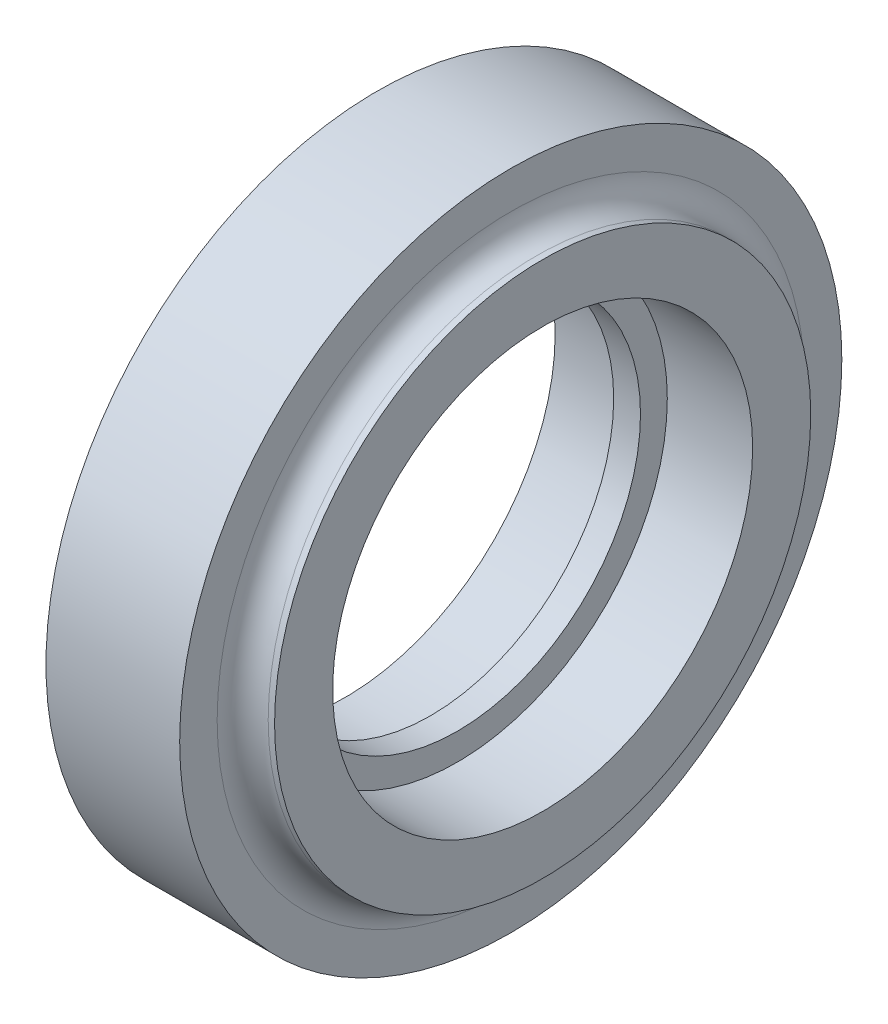
SolidWorks part; units mm, degrees
material "AISI 1020"
ref_plane "Front" through (0, 0, 0) normal (0, 0, 1) x (1, 0, 0)
ref_plane "Top" through (0, 0, 0) normal (0, 1, 0) x (1, 0, 0)
ref_plane "Right" through (0, 0, 0) normal (1, 0, 0) x (0, 0, -1)
sketch "Sketch1" plane through (0, 0, 0) normal (0, 0, 1) x (1, 0, 0)
  line L0 (-4, 0) -> (4, 0) construction
  line L1 (-11.0504, 0) -> (-11.0504, 30)
  line L2 (-11.0504, 30) -> (-10.3365, 30)
  line L3 (-7.4813, 32.8553) -> (-7.4813, 37.1382)
  line L4 (-4.1792, 50) -> (4.1792, 50)
  line L5 (7.4813, 37.1382) -> (7.4813, 32.8553)
  line L6 (10.3365, 30) -> (11.0504, 30)
  line L7 (11.0504, 30) -> (11.0504, 0)
  line L8 (11.0504, 0) -> (-11.0504, 0)
  line L9 (0, 0) -> (0, 50) construction
  line L10 (-6.318, 45.0782) -> (6.318, 45.0782) construction
  line L11 (-6.318, -45.0782) -> (6.318, -45.0782) construction
  line L13 (-7.4813, 37.1382) -> (3.7984, 37.1382) construction
  line L14 (-7.4813, -37.1382) -> (3.7984, -37.1382) construction
  arc A0 (-4.1792, 50) -> (-7.4813, 37.1382) centre (17.9165, 37.4726) ccw
  arc A1 (4.1792, 50) -> (7.4813, 37.1382) centre (-17.9165, 37.4726) cw
  arc A2 (7.4813, 32.8553) -> (10.3365, 30) centre (10.3365, 32.8553) ccw
  arc A3 (-10.3365, 30) -> (-7.4813, 32.8553) centre (-10.3365, 32.8553) ccw
  point P30 (7.4813, 30)
  point P33 (-7.4813, 30)
  point P34 (24, 26.331)
  point P36 (39.88, 26.331)
  point P37 (24, 21.8279)
  point P38 (48.13, 21.8279)
  point P39 (24, 17.1531)
  point P40 (39.75, 17.1531)
  point P41 (24, 13.3224)
  point P42 (53.29, 13.3224)
  point P43 (24, 30.8002)
  point P44 (35, 30.8002)
  point P45 (24, 35.1098)
  point P46 (49.4, 35.1098)
  dimension "D1" = 7.1382
  dimension "rx" = 25.4
  dimension "D3" = 2.8553
  dimension "d" = 90.1564
  dimension "p" = 25.4
  dimension "z" = 11
  dimension "da" = 100
  dimension "df" = 74.2764
  dimension "dr" = 15.88
  dimension "dg" = 60
  dimension "h" = 24.13
  dimension "bf1" = 14.9625
  dimension "b1" = 15.75
  dimension "ba" = 3.302
  dimension "D2" = 3.5691
  dimension "pt" = 29.29
revolve "Revolve" add sketch "Sketch1" angle 360 about L0
ref_axis "Axis1" through (-8.5448, 0, 0) along (1, 0, 0)
sketch "Sketch2" plane through (0, 0, 0) normal (1, 0, 0) x (0, 0, -1)
  line L0 (0, 0) -> (0, 50) construction
  line L1 (0, 0) -> (-14.0866, 47.9746) construction
  line L2 (0, 0) -> (-27.032, 42.0627) construction
  line L3 (6.11, 39.8682) -> (6.6032, 39.4476) construction
  line L4 (8.7167, 43.7328) -> (-9.6667, 53.3211) construction
  line L5 (0, 0) -> (14.0866, 47.9746) construction
  line L6 (8.7167, 43.7328) -> (9.2555, 44.7659)
  line L7 (-8.7167, 43.7328) -> (-9.2555, 44.7659)
  circle A0 centre (0, 0) radius 50 construction
  arc A1 (6.11, 39.8682) -> (-6.11, 39.8682) centre (0, 45.0782) cw
  arc A2 (6.11, 39.8682) -> (8.7167, 43.7328) centre (-9.6667, 53.3211) ccw
  arc A3 (12.2691, 48.4713) -> (9.2555, 44.7659) centre (19.8078, 39.2621) ccw
  arc A4 (-6.11, 39.8682) -> (-8.7167, 43.7328) centre (9.6667, 53.3211) cw
  arc A5 (-12.2691, 48.4713) -> (-9.2555, 44.7659) centre (-19.8078, 39.2621) cw
  arc A7 (12.2691, 48.4713) -> (-12.2691, 48.4713) centre (0, 0) ccw
  dimension "r1" = 8.0297
  dimension "r3" = 11.9013
  dimension "D1" = 32.727
  dimension "D2" = 16.364
  dimension "av2" = 49.545
  dimension "M" = 9.6667
  dimension "T" = 8.2429
  dimension "beta" = 12.909
  dimension "yv2" = 11.182
  dimension "bc" = 1.1652
extrude "ExtrudeCutOne" cut sketch "Sketch2" against normal mid plane 21.6007
pattern_circular "PatternOne" count 11 over 360 about axis through (-4, 0, 0) along (1, 0, 0) of "ExtrudeCutOne"
sketch "SketchHole" plane through (0, 0, 0) normal (1, 0, 0) x (0, 0, -1)
  circle A0 centre (0, 0) radius 23.5
  dimension "D1" = 47
extrude "Cut-ExtrudeA" cut sketch "SketchHole" against normal through all and the other way through all
sketch "草图3" plane through (11.0504, 0, 0) normal (1, 0, 0) x (0, 0, -1)
  circle A0 centre (0, 0) radius 47.0485 construction
  circle A2 centre (0, 0) radius 37.0485
  arc A3 (-1.0862, 37.1223) -> (-19.156, 31.8166) centre (0, 0) ccw construction
  arc A5 (-20.9836, 30.642) -> (-19.156, 31.8166) centre (-24.3711, 37.9222) ccw construction
  dimension "D1" = 10
extrude "切除-拉伸4" cut sketch "草图3" against normal through all flip side to cut
ref_plane "基准面1" through (0, 0, 0) normal (1, 0, 0) x (0, 0, -1)
sketch "草图4" plane through (0, 0, 0) normal (1, 0, 0) x (0, 0, -1)
  circle A0 centre (0, 0) radius 20.5
  circle A1 centre (0, 0) radius 23.5 construction
  circle A2 centre (0, 0) radius 23.5
  dimension "D1" = 41
extrude "凸台-拉伸1" add sketch "草图4" along normal mid plane 3
